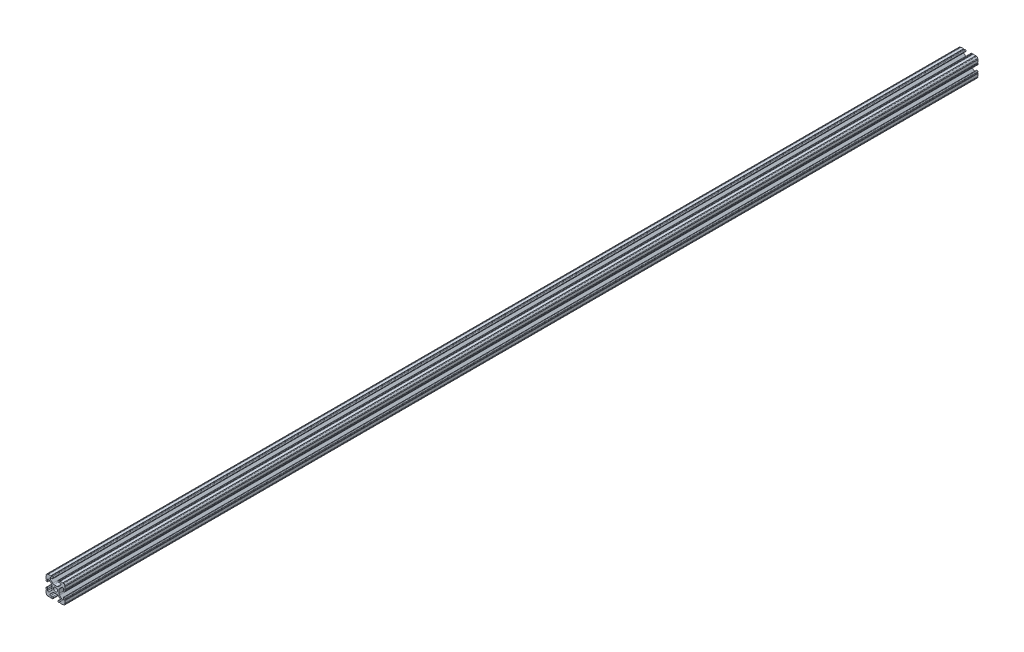
SolidWorks part; units mm, degrees
ref_plane "Front Plane" through (0, 0, 0) normal (0, 0, 1) x (1, 0, 0)
ref_plane "Top Plane" through (0, 0, 0) normal (0, 1, 0) x (1, 0, 0)
ref_plane "Right Plane" through (0, 0, 0) normal (1, 0, 0) x (0, 0, -1)
sketch "Sketch2" plane through (0, 0, 0) normal (0, 0, 1) x (1, 0, 0)
  line L0 (0, 12.7) -> (0, -12.7) construction
  line L1 (-12.7, 0) -> (12.7, 0) construction
  line L2 (3.2512, -12.7) -> (12.7, -12.7)
  line L3 (12.7, -12.7) -> (12.7, -3.2512)
  line L4 (3.2512, -12.7) -> (3.2512, -10.4902)
  line L5 (3.2512, -10.4902) -> (8.9276, -10.4902)
  line L6 (8.9276, -10.4902) -> (3.0856, -4.6482)
  line L7 (0, 0) -> (12.7, -12.7) construction
  line L8 (12.7, -3.2512) -> (10.4902, -3.2512)
  line L9 (10.4902, -3.2512) -> (10.4902, -8.9276)
  line L10 (10.4902, -8.9276) -> (4.6482, -3.0856)
  circle A0 centre (0, 0) radius 2.6035
  arc A1 (6.3485, -10.4902) -> (7.1039, -8.6665) centre (6.3485, -9.4219) ccw construction
  point P8 (0, -4.6482)
  dimension "Center Hole Diameter" = 5.207
  dimension "Rail Height" = 25.4
  dimension "Rail Width" = 25.4
  dimension "T-Slot Width" = 6.5024
  dimension "Slot Inner Width" = 14.8336
  dimension "Thickness" = 2.2098
  dimension "Slot Depth" = 5.842
  dimension "D1" = 2.2098
sketch "Sketch3" plane through (0, 0, 0) normal (1, 0, 0) x (0, 0, -1)
  line L0 (-609.6, -12.7) -> (609.6, -12.7) construction
  line L1 (-584.2, 0) -> (584.2, 0) construction
  dimension "Length" = 1219.2
  dimension "D1" = 25.4
sketch "Sketch4" plane through (0, 0, 0) normal (0, 0, 1) x (1, 0, 0)
  line L0 (4.1904, -12.7) -> (10.1173, -12.7)
  line L1 (3.2512, -12.7) -> (12.7, -12.7) construction
  line L2 (3.2512, -12.7) -> (3.2512, -10.4902) construction
  line L3 (3.2512, -10.4902) -> (8.9276, -10.4902) construction
  line L4 (3.2512, -11.4294) -> (3.2512, -11.7608)
  line L5 (4.1904, -10.4902) -> (6.3485, -10.4902)
  line L6 (0, -4.6482) -> (2.164, -4.6482)
  line L7 (8.9276, -10.4902) -> (3.0856, -4.6482) construction
  line L8 (3.7373, -5.2999) -> (7.1039, -8.6665)
  line L9 (12.7, -12.7) -> (12.7, -3.2512) construction
  line L10 (10.4902, -8.9276) -> (4.6482, -3.0856) construction
  line L11 (10.4902, -3.2512) -> (10.4902, -8.9276) construction
  line L12 (10.4902, -6.3485) -> (10.4902, -4.1904)
  line L13 (12.7, -3.2512) -> (10.4902, -3.2512) construction
  line L14 (11.4294, -3.2512) -> (11.7608, -3.2512)
  line L15 (12.7, -4.1904) -> (12.7, -10.1173)
  line L16 (8.6665, -7.1039) -> (5.2999, -3.7373)
  line L17 (4.6482, 0) -> (4.6482, -2.164)
  line L18 (-12.7, 0) -> (12.7, 0) construction
  line L19 (0, -4.6482) -> (0, -2.6035)
  line L20 (0, 12.7) -> (0, -12.7) construction
  line L21 (4.6482, 0) -> (2.6035, 0)
  arc A0 (3.2512, -11.7608) -> (4.1904, -12.7) centre (4.1904, -11.7608) ccw
  arc A2 (3.2512, -11.4294) -> (4.1904, -10.4902) centre (4.1904, -11.4294) cw
  arc A3 (6.3485, -10.4902) -> (7.1039, -8.6665) centre (6.3485, -9.4219) ccw
  arc A4 (2.164, -4.6482) -> (3.7373, -5.2999) centre (2.164, -6.8732) cw
  arc A5 (10.1173, -12.7) -> (12.7, -10.1173) centre (10.1173, -10.1173) ccw
  arc A6 (8.6665, -7.1039) -> (10.4902, -6.3485) centre (9.4219, -6.3485) ccw
  arc A7 (10.4902, -4.1904) -> (11.4294, -3.2512) centre (11.4294, -4.1904) cw
  arc A8 (11.7608, -3.2512) -> (12.7, -4.1904) centre (11.7608, -4.1904) cw
  arc A9 (5.2999, -3.7373) -> (4.6482, -2.164) centre (6.8732, -2.164) cw
  circle A10 centre (0, 0) radius 2.6035 construction
  arc A11 (0, -2.6035) -> (2.6035, 0) centre (0, 0) ccw
  dimension "D1" = 2.5827
  dimension "D2" = 2.225
  dimension "D3" = 0.9392
extrude "Boss-Extrude1" add sketch "Sketch4" along normal mid plane 1219.2
sketch "Sketch5" plane through (0, 0, 0) normal (0, 0, 1) x (1, 0, 0)
  line L0 (3.2512, -12.7) -> (12.7, -12.7) construction
  line L1 (4.1904, -10.4902) -> (6.3485, -10.4902) construction
  line L3 (0, 0) -> (12.7, -12.7) construction
  line L4 (6.3485, -10.4902) -> (6.3485, -12.7) construction
  line L5 (8.9276, -10.4902) -> (3.0856, -4.6482) construction
  circle A0 centre (10.3562, -12.7) radius 0.5524
  circle A1 centre (5.796, -12.7) radius 0.5524
  circle A2 centre (12.7, -10.3562) radius 0.5524
  circle A3 centre (12.7, -5.796) radius 0.5524
  point P10 (5.2694, -10.4902)
  point P12 (9.4219, -6.3485)
  dimension "D1" = 1.1049
extrude "Cut-Extrude1" cut sketch "Sketch5" against normal through all both and the other way through all
mirror "Mirror1" about plane through (0, 0, 0) normal (1, 0, 0) of bodies 137 134
mirror "Mirror2" about plane through (0, 0, 0) normal (0, 1, 0) of bodies 135
equation "\"D1@Boss-Extrude1\"=\"Length@Sketch3\""
equation "\"D1@Sketch2\"=\"Thickness@Sketch2\""
equation "\"D2@Sketch4\"=\"Slot Inner Width@Sketch2\"*0.15"
equation "\"D1@Sketch4\"=\"D3@Sketch4\"*2.75"
equation "\"D3@Sketch4\"=\"Thickness@Sketch2\"*0.425"
equation "\"D1@Sketch5\"=\"Thickness@Sketch2\"*0.5"
